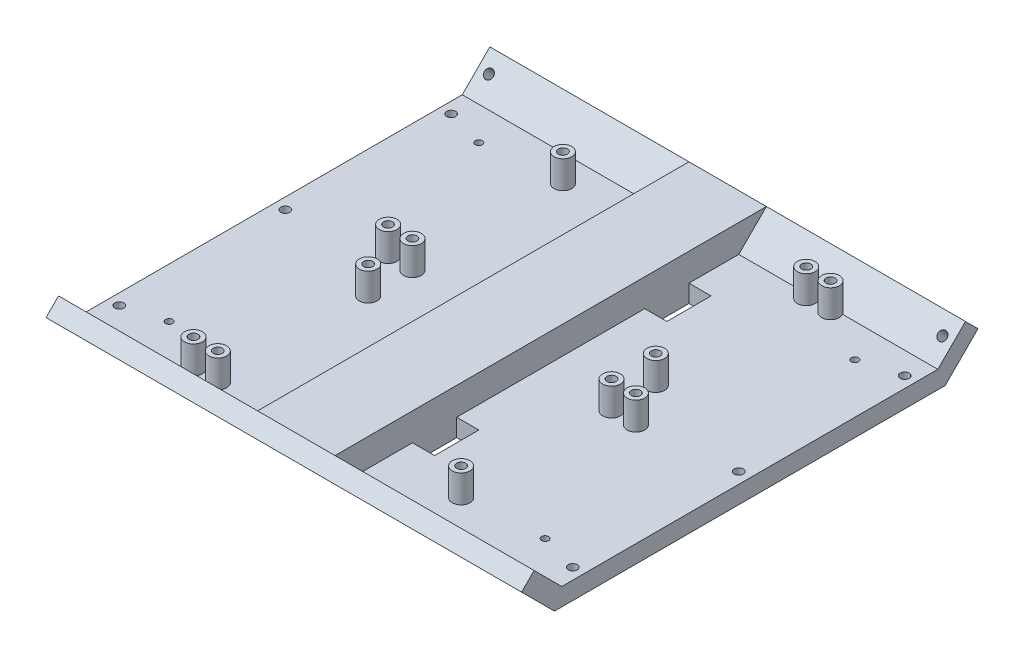
SolidWorks part; units mm, degrees
material "ABS"
ref_plane "Front Plane" through (0, 0, 0) normal (0, 0, 1) x (1, 0, 0)
ref_plane "Top Plane" through (0, 0, 0) normal (0, 1, 0) x (1, 0, 0)
ref_plane "Right Plane" through (0, 0, 0) normal (1, 0, 0) x (0, 0, -1)
sketch "Sketch2" plane through (0, 0, 0) normal (1, 0, 0) x (0, 0, -1)
  line L0 (-85, 0) -> (85, 0)
  line L1 (85, 0) -> (97.5, 12.5)
  line L2 (-85, 0) -> (-97.5, 12.5)
  line L8 (-88.3137, -8) -> (-103.1569, 6.8431)
  line L9 (-88.3137, -8) -> (88.3137, -8)
  line L10 (88.3137, -8) -> (103.1569, 6.8431)
  line L11 (-103.1569, 6.8431) -> (-97.5, 12.5)
  line L12 (97.5, 12.5) -> (103.1569, 6.8431)
  line L13 (-97.5, 12.5) -> (-110, 25) construction
  line L14 (97.5, 12.5) -> (110, 25) construction
  point P4 (0, 0)
  dimension "D2" = 135
  dimension "D3" = 135
  dimension "D1" = 220
  dimension "D4" = 25
  dimension "D5" = 8
extrude "Main" add sketch "Sketch2" along normal mid plane 215
hole_wizard "Ø4.0mm Dowel Hole1" positions "3DSketch1" profile "Sketch3" hole size "Ø4.0" standard "ANSI Metric" end condition through all
sketch3d "3DSketch1"
  line L0 (-107.5, 7.0711, -92.0711) -> (-102.5, 7.0711, -92.0711) construction
  line L1 (-107.5, 12.5, -97.5) -> (-107.5, 0, -85) construction
  line L2 (-102.5, 7.0711, -92.0711) -> (-102.5, 0, -85) construction
  line L3 (107.5, 0, -85) -> (-107.5, 0, -85) construction
  line L4 (-102.5, 0, -85) -> (-102.5, 0, -75) construction
  line L5 (-102.5, 0, -75) -> (-102.5, 0, 0) construction
  line L6 (-102.5, 0, 0) -> (-102.5, 0, 75) construction
  line L7 (-102.5, 0, 75) -> (-102.5, 0, 85) construction
  line L8 (107.5, 0, 85) -> (-107.5, 0, 85) construction
  line L13 (-102.5, 0, 85) -> (-102.5, 7.0711, 92.0711) construction
  line L14 (-102.5, 7.0711, 92.0711) -> (-107.5, 7.0711, 92.0711) construction
  line L15 (-107.5, 0, 85) -> (-107.5, 12.5, 97.5) construction
  line L20 (102.5, 0, -85) -> (102.5, 0, -75) construction
  line L21 (102.5, 0, -75) -> (102.5, 0, 0) construction
  line L22 (102.5, 0, 0) -> (102.5, 0, 75) construction
  line L23 (102.5, 0, 75) -> (102.5, 0, 85) construction
  line L24 (102.5, 0, 85) -> (102.5, 7.0711, 92.0711) construction
  line L25 (102.5, 7.0711, 92.0711) -> (107.5, 7.0711, 92.0711) construction
  line L26 (107.5, 0, 85) -> (107.5, 12.5, 97.5) construction
  line L28 (102.5, 0, -85) -> (102.5, 7.0711, -92.0711) construction
  line L29 (102.5, 7.0711, -92.0711) -> (107.5, 7.0711, -92.0711) construction
  line L30 (107.5, 12.5, -97.5) -> (107.5, 0, -85) construction
  line L32 (107.5, 0, 85) -> (102.5, 0, 85) construction
  line L34 (-102.5, 0, 85) -> (-107.5, 0, 85) construction
  point P0 (-102.5, 7.0711, -92.0711)
  point P2 (-102.5, 0, -75)
  point P4 (-102.5, 0, 0)
  point P6 (-102.5, 0, 75)
  point P8 (-102.5, 7.0711, 92.0711)
  point P10 (102.5, 7.0711, 92.0711)
  point P12 (102.5, 0, 75)
  point P14 (102.5, 0, 0)
  point P16 (102.5, 0, -75)
  point P18 (102.5, 7.0711, -92.0711)
  dimension "D1" = 5
  dimension "D2" = 10
  dimension "D3" = 10
sketch "Sketch3" plane through (-102.5, 7.0711, -92.0711) normal (1, 0, 0) x (0, -0.7071, 0.7071)
  line L0 (0, 0) -> (0, 18.4957)
  line L1 (0, 18.4957) -> (2.05, 18.4957)
  line L2 (2.05, 18.4957) -> (2.05, 0)
  line L5 (2.05, 0) -> (0, 0)
  line L11 (0, -6.35) -> (0, 107.95) construction
  dimension "Thru Hole Dia." = 4.1
  dimension "Thru Hole Depth" = 18.4957
sketch "Sketch4" plane through (0, 0, 0) normal (0, 1, 0) x (1, 0, 0)
  line L0 (0, -85) -> (0, 85) construction
  line L5 (107.5, -85) -> (-107.5, -85) construction
  line L7 (107.5, 85) -> (-107.5, 85) construction
  line L8 (0, 0) -> (107.5, 0) construction
  line L9 (107.5, 85) -> (107.5, -85) construction
  line L11 (17.5, 62.5) -> (27.5, 62.5)
  line L12 (17.5, 62.5) -> (17.5, 42.5)
  line L13 (17.5, 42.5) -> (27.5, 42.5)
  line L14 (27.5, 62.5) -> (27.5, 42.5)
  line L15 (17.5, 62.5) -> (27.5, 42.5) construction
  line L16 (17.5, 42.5) -> (27.5, 62.5) construction
  point P10 (22.5, 52.5)
  dimension "D1" = 20
  dimension "D2" = 10
  dimension "D3" = 35
  dimension "D4" = 125
extrude "Battery strap cutout" cut sketch "Sketch4" against normal through all
mirror "Battery strap cutout mirror" about plane through (0, 0, 0) normal (1, 0, 0) of "Battery strap cutout" second plane through (0, 0, 0) second plane normal (0, 0, 1)
sketch "Sketch6" plane through (0, 0, 0) normal (1, 0, 0) x (0, 0, -1)
  line L0 (-97.5, 12.5) -> (97.5, 12.5)
  line L1 (-85, 0) -> (-97.5, 12.5) construction
  line L2 (97.5, 12.5) -> (85, 0) construction
  line L3 (85, 0) -> (-85, 0) construction
  line L4 (-85, 0) -> (-97.5, 12.5)
  line L5 (85, 0) -> (-85, 0)
  line L6 (97.5, 12.5) -> (85, 0)
extrude "Battery mount" add sketch "Sketch6" along normal mid plane 35
sketch "Sketch7" plane through (0, 12.5, 0) normal (0, 1, 0) x (1, 0, 0)
  line L0 (-61, -15) -> (-50, -15) construction
  line L1 (-61, -15) -> (-61, -83) construction
  line L2 (-61, -83) -> (-50, -83) construction
  line L3 (-50, -15) -> (-50, -83) construction
  line L4 (-61, -15) -> (-50, -83) construction
  line L5 (-61, -83) -> (-50, -15) construction
  line L6 (-61, 73) -> (-50, 73) construction
  line L7 (-61, 73) -> (-61, 5) construction
  line L8 (-61, 5) -> (-50, 5) construction
  line L9 (-50, 73) -> (-50, 5) construction
  line L10 (-61, 73) -> (-50, 5) construction
  line L11 (-61, 5) -> (-50, 73) construction
  line L12 (50, 83) -> (61, 83) construction
  line L13 (50, 83) -> (50, 15) construction
  line L14 (50, 15) -> (61, 15) construction
  line L15 (61, 83) -> (61, 15) construction
  line L16 (50, 83) -> (61, 15) construction
  line L17 (50, 15) -> (61, 83) construction
  line L18 (50, -5) -> (61, -5) construction
  line L19 (50, -5) -> (50, -73) construction
  line L20 (50, -73) -> (61, -73) construction
  line L21 (61, -5) -> (61, -73) construction
  line L22 (50, -5) -> (61, -73) construction
  line L23 (50, -73) -> (61, -5) construction
  circle A0 centre (-50, -15) radius 4
  circle A1 centre (-50, -83) radius 4
  circle A2 centre (-61, -83) radius 4
  circle A3 centre (-50, 73) radius 4
  circle A4 centre (-50, 5) radius 4
  circle A5 centre (-61, 5) radius 4
  circle A6 centre (61, 83) radius 4
  circle A7 centre (50, 83) radius 4
  circle A8 centre (50, 15) radius 4
  circle A9 centre (61, -5) radius 4
  circle A10 centre (50, -5) radius 4
  circle A11 centre (50, -73) radius 4
  point P0 (-55.5, -49)
  point P8 (55.5, 49)
  point P9 (-55.5, 39)
  point P18 (55.5, -39)
  dimension "D3" = 8
  dimension "D1" = 68
  dimension "D2" = 11
  dimension "D4" = 5
  dimension "D5" = 15
  dimension "D6" = 15
  dimension "D7" = 5
  dimension "D8" = 50
  dimension "D9" = 50
extrude "PCB mounts" add sketch "Sketch7" against normal up to surface (12.5 mm away) up to face at (35.8333, 0, 0)
sketch "Sketch8" plane through (0, 12.5, 0) normal (0, 1, 0) x (1, 0, 0)
  circle A0 centre (-50, 73) radius 2.05
  circle A1 centre (-50, 5) radius 2.05
  circle A2 centre (-61, 5) radius 2.05
  circle A3 centre (-50, -15) radius 2.05
  circle A4 centre (-61, -83) radius 2.05
  circle A5 centre (-50, -83) radius 2.05
  circle A6 centre (50, -73) radius 2.05
  circle A7 centre (61, -5) radius 2.05
  circle A8 centre (50, -5) radius 2.05
  circle A9 centre (50, 15) radius 2.05
  circle A10 centre (61, 83) radius 2.05
  circle A11 centre (50, 83) radius 2.05
  dimension "D1" = 4.1
extrude "PCB mount inserts" cut sketch "Sketch8" against normal blind 5.7
sketch "Sketch9" plane through (0, -8, 0) normal (0, -1, 0) x (1, 0, 0)
  circle A0 centre (85, 70) radius 1.6
  dimension "D1" = 3.2
  dimension "D2" = 85
  dimension "D3" = 70
extrude "Feet screw hole" cut sketch "Sketch9" against normal through all
mirror "Mirror1" about plane through (0, 0, 0) normal (0, 0, 1) of "Feet screw hole" second plane through (0, 0, 0) second plane normal (1, 0, 0)
equation "\"length\" = 215mm"
equation "\"D1@Main\" = \"length\""
equation "\"width\" = 220mm"
equation "\"height\" = 100mm"
equation "\"skin_th\" = 8mm"
equation "\"D5@Sketch2\"=\"skin_th\""
equation "\"D1@Sketch2\"=\"width\""
